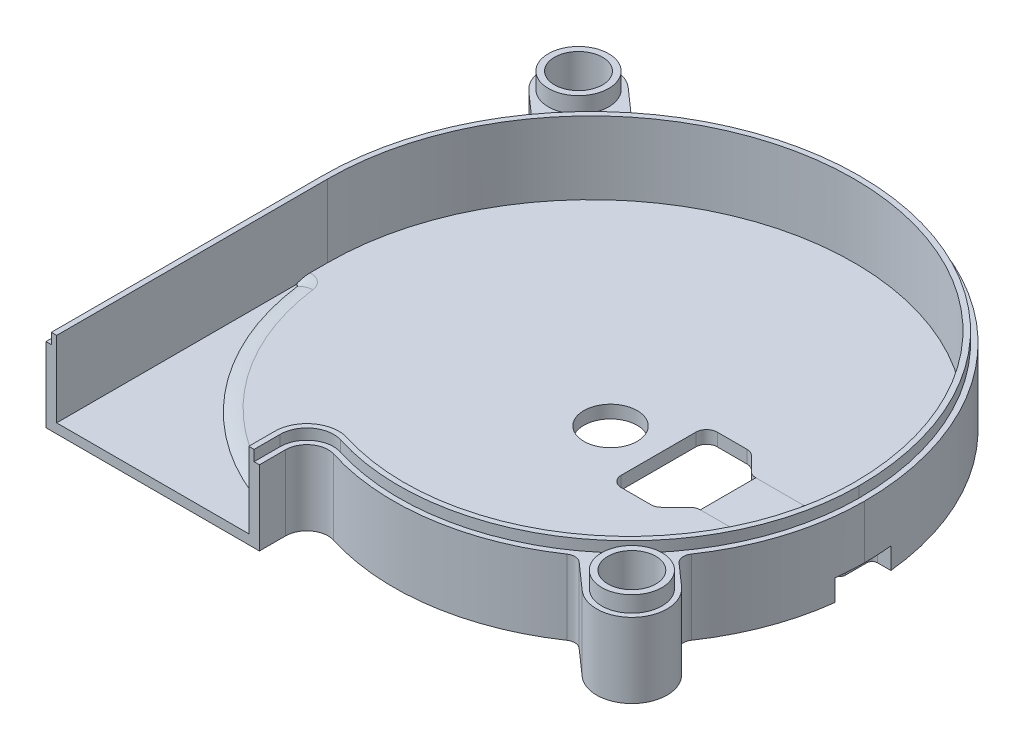
SolidWorks part; units mm, degrees
material "PET"
ref_plane "Спереди" through (0, 0, 0) normal (0, 0, 1) x (1, 0, 0)
ref_plane "Сверху" through (0, 0, 0) normal (0, 1, 0) x (1, 0, 0)
ref_plane "Справа" through (0, 0, 0) normal (1, 0, 0) x (0, 0, -1)
sketch "Эскиз1" plane through (0, 0, 0) normal (0, 1, 0) x (1, 0, 0)
  line L0 (0, -37.0288) -> (0, 52.769) construction
  line L1 (-41.2177, 0) -> (28.9689, 0) construction
  line L2 (-27.5, -25.4) -> (-7.5, -25.4)
  line L3 (-7.5, -25.4) -> (-7.5, -22.9558)
  line L4 (-27.5, -25.4) -> (-27.5, 0)
  line L5 (17.8147, -20.4728) -> (22.1853, -15.5272) construction
  line L6 (-25.1853, 17.5272) -> (-20.8147, 22.4728) construction
  line L7 (-23, 20) -> (20, -18) construction
  line L8 (-20.8147, 22.4728) -> (-18.5989, 20.5146)
  line L9 (-25.1853, 17.5272) -> (-23.2069, 15.7789)
  line L10 (17.8147, -20.4728) -> (15.377, -18.3185)
  line L11 (22.1853, -15.5272) -> (20.1437, -13.7231)
  circle A0 centre (0, 0) radius 16 construction
  arc A1 (23.8, 0) -> (-17.3331, 20.4667) centre (-1.85, 0.0168) ccw
  circle A2 centre (-23, 20) radius 2.25
  circle A3 centre (20, -18) radius 2.25
  arc A4 (23.8, 0) -> (19.9791, -12.4113) centre (1.7319, 0) cw
  arc A5 (22.1853, -15.5272) -> (17.8147, -20.4728) centre (20, -18) cw
  arc A6 (-25.1853, 17.5272) -> (-20.8147, 22.4728) centre (-23, 20) cw
  arc A7 (14.152, -18.2412) -> (-4.899, -21.0483) centre (1.7319, 0) cw
  arc A8 (-23.0428, 14.4662) -> (-27.5, 0) centre (-1.85, 0.0168) ccw
  arc A9 (-4.899, -21.0483) -> (-7.5, -22.9558) centre (-5.5, -22.9558) ccw
  arc A10 (-18.5989, 20.5146) -> (-17.3331, 20.4667) centre (-17.9367, 21.2639) ccw
  arc A11 (-23.2069, 15.7789) -> (-23.0428, 14.4662) centre (-23.8691, 15.0296) cw
  arc A12 (20.1437, -13.7231) -> (19.9791, -12.4113) centre (20.8059, -12.9738) cw
  arc A13 (15.377, -18.3185) -> (14.152, -18.2412) centre (14.7148, -19.0678) ccw
  circle A14 centre (0, 0) radius 2.5
  point P14 (0, 25.6)
  point P16 (16, 0)
  point P17 (0, -22)
  point P20 (23.8, 0)
  point P26 (0, -16)
  point P34 (-22.5346, 15.1848)
  point P41 (14.784, -17.7945)
  dimension "D5" = 4.5
  dimension "D11" = 3.3
  dimension "D6" = 32
  dimension "D14" = 2
  dimension "D15" = 1
  dimension "D16" = 5
  dimension "D1" = 18
  dimension "D2" = 20
  dimension "D3" = 23
  dimension "D4" = 20
  dimension "D7" = 51.3
  dimension "D8" = 51
  dimension "D9" = 20
  dimension "D10" = 25.4
  dimension "D12" = 7.8
  dimension "D13" = 6
extrude "Бобышка-Вытянуть1" add sketch "Эскиз1" along normal blind 8
sketch "Эскиз2" plane through (0, 8, 0) normal (0, 1, 0) x (1, 0, 0)
  line L0 (-27.5, 0) -> (-27.5, -25.4) construction
  line L1 (-27.5, -25.4) -> (-7.5, -25.4) construction
  line L5 (-7.5, -25.4) -> (-7.5, -22.9558) construction
  line L12 (-27.5, 0) -> (-27.5, -25.4) construction
  line L13 (-27.5, -25.4) -> (-7.5, -25.4) construction
  line L14 (-7.5, -25.4) -> (-7.5, -22.9558) construction
  line L15 (-8.5, -25.4) -> (-8.5, -22.9558)
  line L16 (-26.5, 0.0003) -> (-26.5, -25.4)
  line L17 (-8.5, -25.4) -> (-26.5, -25.4)
  arc A0 (-23.0428, 14.4662) -> (-27.5, 0) centre (-1.85, 0.0168) ccw construction
  arc A1 (23.8, 0) -> (-17.3331, 20.4667) centre (-1.85, 0.0168) ccw construction
  arc A2 (19.9791, -12.4113) -> (23.8, 0) centre (1.7319, 0) ccw construction
  arc A4 (-4.899, -21.0483) -> (14.152, -18.2412) centre (1.7319, 0) ccw construction
  arc A5 (-4.899, -21.0483) -> (-7.5, -22.9558) centre (-5.5, -22.9558) ccw construction
  arc A19 (-23.0428, 14.4662) -> (-27.5, 0) centre (-1.85, 0.0168) ccw construction
  arc A20 (23.8, 0) -> (-17.3331, 20.4667) centre (-1.85, 0.0168) ccw construction
  arc A21 (19.9791, -12.4113) -> (23.8, 0) centre (1.7319, 0) ccw construction
  arc A22 (-4.899, -21.0483) -> (14.152, -18.2412) centre (1.7319, 0) ccw construction
  arc A23 (-4.899, -21.0483) -> (-7.5, -22.9558) centre (-5.5, -22.9558) ccw construction
  arc A24 (-23.0428, 14.4662) -> (-17.3331, 20.4667) centre (-1.85, 0.0168) cw construction
  arc A25 (14.152, -18.2412) -> (19.9791, -12.4113) centre (1.7319, 0) ccw construction
  arc A26 (-4.5986, -20.0945) -> (-8.5, -22.9558) centre (-5.5, -22.9558) ccw
  arc A27 (-4.5986, -20.0945) -> (13.5892, -17.4146) centre (1.7319, 0) ccw
  arc A28 (13.5892, -17.4146) -> (19.1522, -11.8489) centre (1.7319, 0) ccw
  arc A29 (19.1522, -11.8489) -> (22.8, 0.0003) centre (1.7319, 0) ccw
  arc A30 (22.8, 0.0003) -> (-16.7295, 19.6694) centre (-1.85, 0.0168) ccw
  arc A31 (-22.2166, 13.9029) -> (-16.7295, 19.6694) centre (-1.85, 0.0168) cw
  arc A32 (-22.2166, 13.9029) -> (-26.5, 0.0003) centre (-1.85, 0.0168) ccw
  dimension "D1" = 1
extrude "Вырез-Вытянуть1" cut sketch "Эскиз2" against normal offset from surface (6.8 mm away) 1.2 up to face at (20, 0, 20.25)
sketch "Эскиз3" plane through (0, 8, 0) normal (0, 1, 0) x (1, 0, 0)
  line L0 (-8.5, -25.4) -> (-8.5, -22.9558) construction
  line L1 (-26.5, 0.0003) -> (-26.5, -25.4) construction
  line L2 (-8.5, -25.4) -> (-8.5, -22.9558) construction
  line L3 (-26.5, 0.0003) -> (-26.5, -25.4) construction
  line L4 (-8, -25.4) -> (-8, -22.9558)
  line L5 (-27, 0.0002) -> (-27, -25.4)
  line L6 (-27, -25.4) -> (-8, -25.4)
  arc A0 (-4.5986, -20.0945) -> (-8.5, -22.9558) centre (-5.5, -22.9558) ccw construction
  arc A1 (-4.5986, -20.0945) -> (22.8, 0.0003) centre (1.7319, 0) ccw construction
  arc A2 (22.8, 0.0003) -> (-26.5, 0.0003) centre (-1.85, 0.0168) ccw construction
  arc A3 (-4.5986, -20.0945) -> (-8.5, -22.9558) centre (-5.5, -22.9558) ccw construction
  arc A4 (-4.5986, -20.0945) -> (22.8, 0.0003) centre (1.7319, 0) ccw construction
  arc A5 (22.8, 0.0003) -> (-26.5, 0.0003) centre (-1.85, 0.0168) ccw construction
  arc A6 (-4.7488, -20.5714) -> (-8, -22.9558) centre (-5.5, -22.9558) ccw
  arc A7 (-4.7488, -20.5714) -> (23.3, 0.0001) centre (1.7319, 0) ccw
  arc A8 (23.3, 0.0001) -> (-27, 0.0002) centre (-1.85, 0.0168) ccw
  dimension "D1" = 0.5
extrude "Вырез-Вытянуть4" cut sketch "Эскиз3" against normal blind 1 flip side to cut
sketch "Эскиз5" plane through (0, 7, 0) normal (0, 1, 0) x (1, 0, 0)
  circle A0 centre (-23, 20) radius 2.25 construction
  circle A1 centre (-23, 20) radius 2.25
  circle A2 centre (20, -18) radius 2.25 construction
  circle A3 centre (20, -18) radius 2.25
  circle A4 centre (20, -18) radius 2.825
  circle A6 centre (-23, 20) radius 2.825
  dimension "D1" = 5.65
extrude "Бобышка-Вытянуть2" add sketch "Эскиз5" along normal blind 1.5
sketch "Эскиз6" plane through (0, 0, 0) normal (0, -1, 0) x (1, 0, 0)
  line L0 (0, -22.5511) -> (0, 21.8657) construction
  line L1 (22.353, 0) -> (-21.1813, 0) construction
  line L2 (-15.4541, -15.4541) -> (15.4541, 15.4541) construction
  line L3 (16.4933, -16.4933) -> (-15.9867, 15.9867) construction
  line L4 (-12.0793, -12.7864) -> (-12.7864, -12.0793)
  line L5 (-19.6794, -0.5) -> (-19.6794, 0.5)
  line L6 (-11.5092, 10.8021) -> (-10.8021, 11.5092)
  line L7 (-0.5, 17.5691) -> (0.5, 17.5691)
  line L8 (11.9344, 11.2273) -> (11.2273, 11.9344)
  line L9 (18.1489, 3.35) -> (18.1489, -3.35)
  line L10 (9.6758, -10.3829) -> (10.3829, -9.6758)
  line L11 (-0.5, -18.6909) -> (0.5, -18.6909)
  line L12 (-15.1122, -15.8193) -> (-8.1244, -8.8315)
  line L13 (-15.788, -15.0809) -> (-8.8315, -8.1244)
  line L14 (-21.1912, -0.5) -> (-11.9896, -0.5)
  line L15 (-21.1599, 0.5) -> (-11.9896, 0.5)
  line L16 (-15.1339, 14.4268) -> (-8.8315, 8.1244)
  line L17 (-14.4268, 15.1339) -> (-8.1244, 8.8315)
  line L18 (-0.5, 21.1599) -> (-0.5, 11.9896)
  line L19 (0.5, 21.1912) -> (0.5, 11.9896)
  line L20 (15.8193, 15.1122) -> (8.8315, 8.1244)
  line L21 (15.0809, 15.788) -> (8.1244, 8.8315)
  line L22 (22.3989, -3.35) -> (11.5229, -3.35)
  line L23 (22.1865, 3.35) -> (11.5229, 3.35)
  line L24 (15.7966, -16.5037) -> (8.1244, -8.8315)
  line L25 (16.5037, -15.7966) -> (8.8315, -8.1244)
  line L26 (-0.5, -22.5297) -> (-0.5, -11.9896)
  line L27 (0.5, -11.9896) -> (0.5, -22.561)
  arc A0 (22.1865, 3.35) -> (15.8193, 15.1122) centre (0.6849, -0.6849) ccw
  arc A1 (11.5229, 3.35) -> (8.8315, 8.1244) centre (0, 0) ccw
  arc A2 (8.8315, -8.1244) -> (11.5229, -3.35) centre (0, 0) ccw
  arc A3 (16.5037, -15.7966) -> (22.3989, -3.35) centre (0.6849, -0.6849) ccw
  arc A4 (0.5, -22.561) -> (15.7966, -16.5037) centre (0.6849, -0.6849) ccw
  arc A5 (0.5, -11.9896) -> (8.1244, -8.8315) centre (0, 0) ccw
  arc A6 (-8.1244, -8.8315) -> (-0.5, -11.9896) centre (0, 0) ccw
  arc A7 (-15.1122, -15.8193) -> (-0.5, -22.5297) centre (0.6849, -0.6849) ccw
  arc A8 (-21.1912, -0.5) -> (-15.788, -15.0809) centre (0.6849, -0.6849) ccw
  arc A9 (-11.9896, -0.5) -> (-8.8315, -8.1244) centre (0, 0) ccw
  arc A10 (-15.1339, 14.4268) -> (-21.1599, 0.5) centre (0.6849, -0.6849) ccw
  arc A11 (-8.8315, 8.1244) -> (-11.9896, 0.5) centre (0, 0) ccw
  arc A12 (-0.5, 11.9896) -> (-8.1244, 8.8315) centre (0, 0) ccw
  arc A13 (-0.5, 21.1599) -> (-14.4268, 15.1339) centre (0.6849, -0.6849) ccw
  arc A14 (15.0809, 15.788) -> (0.5, 21.1912) centre (0.6849, -0.6849) ccw
  arc A15 (8.1244, 8.8315) -> (0.5, 11.9896) centre (0, 0) ccw
  point P12 (0.6849, -0.6849)
  point P15 (-12.4329, -12.4329)
  point P18 (-19.6794, 0)
  point P26 (0, 17.5691)
  point P29 (11.5808, 11.5808)
  point P32 (18.1489, 0)
  point P35 (10.0294, -10.0294)
  point P38 (0, -18.6909)
  point P39 (-11.1557, 11.1557)
  dimension "D1" = 6.7
  dimension "D2" = 45
  dimension "D4" = 24
  dimension "D3" = 45
  dimension "D5" = 1
extrude "Вырез-Вытянуть5" cut sketch "Эскиз6" against normal blind 0.5
sketch "Эскиз7" plane through (0, 0, 0) normal (0, -1, 0) x (1, 0, 0)
  line L0 (23.6696, -2.6) -> (10.6, -2.6)
  line L1 (10.6, -2.6) -> (8.7, -4.5)
  line L2 (8.7, -4.5) -> (4.5, -4.5)
  line L3 (4.5, -4.5) -> (4.5, 4.5)
  line L4 (4.5, 4.5) -> (8.7, 4.5)
  line L5 (10.6, 2.6) -> (8.7, 4.5)
  line L6 (10.6, 2.6) -> (23.6463, 2.6)
  line L7 (0, 0) -> (30.967, 0) construction
  line L10 (20.3302, 2.6) -> (20.3302, -2.6) construction
  arc A0 (23.8, 0) -> (19.9791, 12.4113) centre (1.7319, 0) ccw construction
  arc A3 (-17.3331, -20.4667) -> (23.8, 0) centre (-1.85, -0.0168) ccw construction
  arc A4 (23.8, 0) -> (23.6463, 2.6) centre (1.7319, 0) ccw
  arc A5 (23.6696, -2.6) -> (23.8, 0) centre (-1.85, -0.0168) ccw
  point P17 (4.5, 0)
  point P19 (20.3302, 0)
  dimension "D1" = 9
  dimension "D2" = 4.2
  dimension "D3" = 4.5
  dimension "D4" = 45
  dimension "D5" = 45
  dimension "D6" = 5.2
extrude "Вырез-Вытянуть6" cut sketch "Эскиз7" against normal blind 2
fillet "Скругление1" radius 1 6 edges at (4.5, 0.6, 4.5) (10.6, 0.6, 2.6) (8.7, 0.6, 4.5) (4.5, 0.6, -4.5) (8.7, 0.6, -4.5) (10.6, 0.6, -2.6)
sketch "Эскиз8" plane through (0, 0, -2.6) normal (0, 0, 1) x (1, 0, 0)
  line L1 (19.4196, 0.8) -> (21.9196, 0.8)
  line L2 (19.4196, 0.8) -> (19.4196, 0)
  line L3 (19.4196, 0) -> (21.9196, 0)
  line L4 (21.9196, 0.8) -> (21.9196, 0)
  line L5 (19.4196, 0.8) -> (21.9196, 0) construction
  line L6 (19.4196, 0) -> (21.9196, 0.8) construction
  line L7 (11.0142, 0) -> (23.6696, 0) construction
  line L8 (23.6696, 2) -> (23.6696, 0) construction
  point P0 (20.6696, 0.4)
  dimension "D1" = 2.5
  dimension "D2" = 3
  dimension "D3" = 0.8
extrude "Бобышка-Вытянуть4" add sketch "Эскиз8" along normal blind 3
fillet "Скругление2" radius 0.5 4 edges at (19.4196, 0.4, -2.6) (19.4196, 0.4, 0.4) (21.9196, 0.4, 0.4) (21.9196, 0.4, -2.6)
sketch "Эскиз9" plane through (0, 1.2, 0) normal (0, 1, 0) x (1, 0, 0)
  line L0 (-26.5, -25.4) -> (-8.5, -25.4) construction
  line L1 (-8.5, -25.4) -> (-8.5, -22.9558) construction
  line L2 (-8.5, -22.9558) -> (-8.5, -25.4)
  line L3 (-8.5, -25.4) -> (-26.5, -25.4)
  line L4 (-26.5, -25.4) -> (-26.5, 0.0003)
  arc A0 (-4.5986, -20.0945) -> (22.639, -2.6) centre (1.7319, 0) ccw construction
  arc A1 (-8.5, -22.9558) -> (-26.5, 0.0003) centre (-2.8413, 0.0161) cw
  arc A2 (22.6643, 2.6) -> (-26.5, 0.0003) centre (-1.85, 0.0168) ccw construction
  arc A3 (-4.5986, -20.0945) -> (22.639, -2.6) centre (1.7319, 0) ccw construction
  arc A4 (22.6643, 2.6) -> (-26.5, 0.0003) centre (-1.85, 0.0168) ccw construction
  arc A5 (-4.5986, -20.0945) -> (-8.5, -22.9558) centre (-5.5, -22.9558) ccw construction
extrude "Вырез-Вытянуть7" cut sketch "Эскиз9" against normal blind 0.3
fillet "Скругление3" radius 0.1 1 edges at (-26.5, 1.05, -0.0003)
fillet "Скругление4" radius 3 2 edges at (-26.4065, 1.2, 2.9604) (-20.4781, 1.2, 15.7534)
sketch "Эскиз10" plane through (0, 1.2, 0) normal (0, 1, 0) x (1, 0, 0)
  line L0 (11.0142, 2.6) -> (11.0142, -2.6)
  line L1 (11.0142, -2.6) -> (15.5142, -2.6)
  line L2 (22.639, -2.6) -> (11.0142, -2.6) construction
  line L3 (15.5142, -2.6) -> (15.5142, 2.6)
  line L4 (11.0142, 2.6) -> (22.6643, 2.6) construction
  line L5 (15.5142, 2.6) -> (11.0142, 2.6)
  dimension "D1" = 4.5
extrude "Бобышка-Вытянуть5" add sketch "Эскиз10" against normal blind 0.5 separate body
equation "\"D11@Эскиз1\"=6.6/2"
